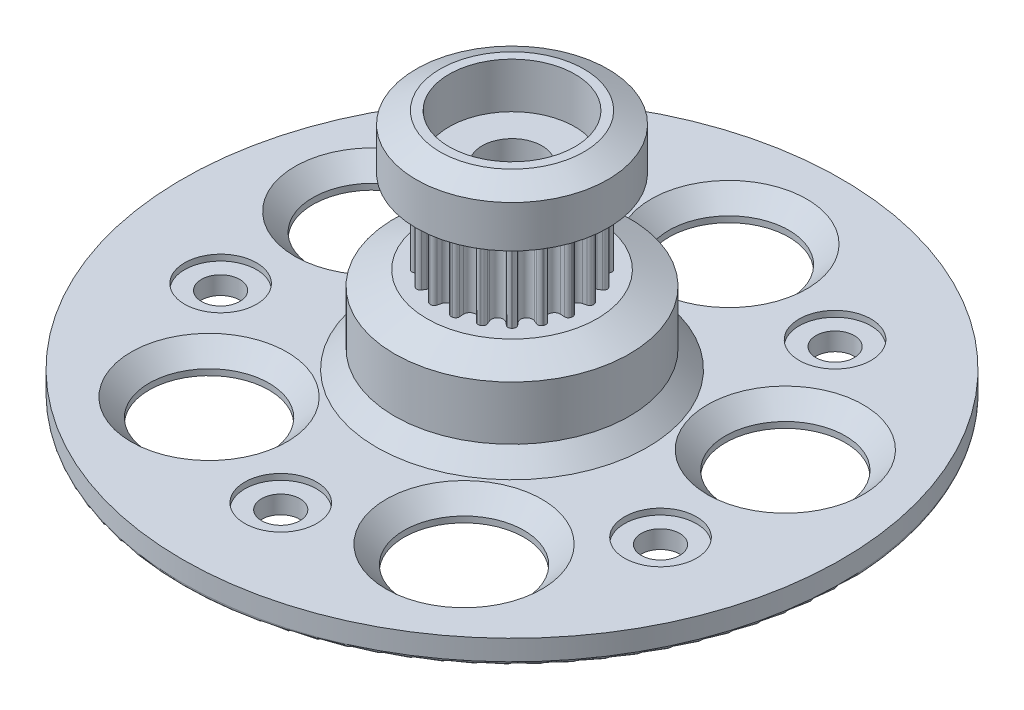
SolidWorks part; units mm, degrees
ref_plane "Frente" through (0, 0, 0) normal (0, 0, 1) x (1, 0, 0)
ref_plane "Topo" through (0, 0, 0) normal (0, 1, 0) x (1, 0, 0)
ref_plane "Lateral" through (0, 0, 0) normal (1, 0, 0) x (0, 0, -1)
sketch "Sketch1" plane through (0, 0, 0) normal (0, 1, 0) x (1, 0, 0)
  circle A0 centre (0, 0) radius 27.5
  dimension "D1" = 55
extrude "Boss-Extrude1" add sketch "Sketch1" along normal blind 2
sketch "Sketch2" plane through (0, 2, 0) normal (0, 1, 0) x (1, 0, 0)
  circle A0 centre (0, 0) radius 9.8
  dimension "D1" = 19.6
extrude "Boss-Extrude2" add sketch "Sketch2" along normal blind 6
chamfer "Chamfer1" distance 1.5 angle 45 1 edges at (0, 2, 9.8)
sketch "Sketch3" plane through (0, 8, 0) normal (0, 1, 0) x (1, 0, 0)
  circle A1 centre (0, 0) radius 9.8
  circle A2 centre (0, 0) radius 9.8
  dimension "D1" = 0
extrude "Boss-Extrude3" add sketch "Sketch3" along normal blind 1.2 draft 66
sketch "Sketch5" plane through (0, 9.2, 0) normal (0, 1, 0) x (1, 0, 0)
  circle A0 centre (0, 0) radius 6
  dimension "D1" = 12
extrude "Boss-Extrude4" add sketch "Sketch5" along normal blind 6
sketch "Sketch7" plane through (0, 15.2, 0) normal (0, 1, 0) x (1, 0, 0)
  line L0 (0, 5.5) -> (0, 0) construction
  line L1 (-0.4851, 5.379) -> (-0.6317, 5.9667)
  line L2 (0.4851, 5.379) -> (0.6317, 5.9667)
  arc A0 (-0.4851, 5.379) -> (0.4851, 5.379) centre (0, 5.5) ccw
  circle A1 centre (0, 0) radius 6 construction
  circle A2 centre (0, 0) radius 6 construction
  arc A3 (0.6317, 5.9667) -> (-0.6317, 5.9667) centre (0, 0) ccw
  dimension "D1" = 1
  dimension "D2" = 14
  dimension "D3" = 14
extrude "Cut-Extrude1" cut sketch "Sketch7" against normal up to surface (6 mm away) up to face at (0, 9.2, 6)
ref_axis "Axis1" through (0, 8, 0) along (0, -1, 0)
pattern_circular "CirPattern1" count 20 over 360 about axis through (0, 8, 0) along (0, -1, 0) of "Cut-Extrude1"
fillet "Fillet1" radius 0.3 40 edges at (0.6317, 12.2, -5.9667) (-0.6317, 12.2, -5.9667) (1.2431, 12.2, -5.8698) (-1.2431, 12.2, -5.8698) (2.4445, 12.2, -5.4794) (2.9961, 12.2, -5.1984) (4.0181, 12.2, -4.4558) (5.1984, 12.2, -2.9961) (4.4558, 12.2, -4.0181) (5.4794, 12.2, -2.4445) (5.8698, 12.2, -1.2431) (5.9667, 12.2, -0.6317) (5.9667, 12.2, 0.6317) (5.8698, 12.2, 1.2431) (5.4794, 12.2, 2.4445) (5.1984, 12.2, 2.9961) (4.4558, 12.2, 4.0181) (4.0181, 12.2, 4.4558) (2.9961, 12.2, 5.1984) (2.4445, 12.2, 5.4794) (1.2431, 12.2, 5.8698) (0.6317, 12.2, 5.9667) (-0.6317, 12.2, 5.9667) (-1.2431, 12.2, 5.8698) (-2.9961, 12.2, 5.1984) (-4.0181, 12.2, 4.4558) (-4.4558, 12.2, 4.0181) (-5.1984, 12.2, 2.9961) (-5.4794, 12.2, 2.4445) (-5.8698, 12.2, 1.2431) (-5.9667, 12.2, 0.6317) (-5.9667, 12.2, -0.6317) (-5.8698, 12.2, -1.2431) (-5.4794, 12.2, -2.4445) (-5.1984, 12.2, -2.9961) (-4.4558, 12.2, -4.0181) (-4.0181, 12.2, -4.4558) (-2.9961, 12.2, -5.1984) (-2.4445, 12.2, -5.4794) (-2.4445, 12.2, 5.4794)
sketch "Sketch9" plane through (0, 0, 0) normal (1, 0, 0) x (0, 0, -1)
  line L0 (0, 15.2) -> (6, 15.2)
  line L1 (0.4851, 15.2) -> (-0.4851, 15.2) construction
  line L2 (6, 15.2) -> (8, 16.2)
  line L3 (8, 16.2) -> (8, 19.7)
  line L4 (8, 19.7) -> (6, 20.7)
  line L5 (6, 20.7) -> (5.25, 20.7)
  line L6 (5.25, 20.7) -> (5.25, 16.9)
  line L7 (5.25, 16.9) -> (0, 16.9)
  line L8 (0, 16.9) -> (0, 15.2)
  dimension "D1" = 6
  dimension "D2" = 8
  dimension "D3" = 1
  dimension "D4" = 1
  dimension "D5" = 5.5
  dimension "D6" = 5.25
  dimension "D7" = 2
  dimension "D8" = 3.8
revolve "Revolve1" add sketch "Sketch9" angle 360 about L8
sketch "Sketch10" plane through (0, 2, 0) normal (0, 1, 0) x (1, 0, 0)
  line L0 (0, 11.3) -> (0, 13.1) construction
  line L1 (0, 13.1) -> (0, 27.5) construction
  circle A4 centre (0, 18.1) radius 5
  circle A7 centre (0, 0) radius 11.3 construction
  circle A8 centre (0, 0) radius 27.5 construction
  dimension "D1" = 10
  dimension "D2" = 1.8
extrude "Cut-Extrude2" cut sketch "Sketch10" against normal through all
chamfer "Chamfer2" distance 1.5 angle 45 1 edges at (0, 2, -13.1)
sketch "Sketch11" plane through (0, 2, 0) normal (0, 1, 0) x (1, 0, 0)
  line L0 (0, 0) -> (-11.3443, 15.614) construction
  line L1 (0, 0) -> (0, 19.3) construction
  circle A0 centre (0, 0) radius 19.3 construction
  circle A1 centre (0, 0) radius 11.3 construction
  circle A2 centre (-11.3443, 15.614) radius 1.6
  dimension "D1" = 8
  dimension "D3" = 3.2
  dimension "D2" = 36
extrude "Cut-Extrude3" cut sketch "Sketch11" against normal through all
sketch "Sketch12" plane through (0, 2, 0) normal (0, 1, 0) x (1, 0, 0)
  circle A0 centre (-11.3443, 15.614) radius 3
  dimension "D1" = 6
extrude "Cut-Extrude4" cut sketch "Sketch12" against normal blind 0.5
pattern_circular "CirPattern2" count 5 over 360 about axis through (0, 8, 0) along (0, -1, 0) of "Cut-Extrude2", "Chamfer2", "Cut-Extrude3", "Cut-Extrude4"
sketch "Sketch13" plane through (0, 0, 0) normal (0, -1, 0) x (1, 0, 0)
  circle A0 centre (0, 0) radius 8.2
  dimension "D1" = 16.4
extrude "Cut-Extrude5" cut sketch "Sketch13" against normal blind 6.8
sketch "Sketch15" plane through (0, 0, 0) normal (0, -1, 0) x (1, 0, 0)
  line L1 (2.15, -10.9131) -> (-2.15, -10.9131)
  line L2 (2.15, -10.9131) -> (2.15, 0)
  line L3 (2.15, 0) -> (-2.15, 0)
  line L4 (-2.15, -10.9131) -> (-2.15, 0)
  circle A0 centre (0, 0) radius 8.2 construction
  arc A1 (-2.15, -7.9131) -> (2.15, -7.9131) centre (0, 0) ccw construction
  dimension "D1" = 4.3
  dimension "D2" = 3
extrude "Cut-Extrude6" cut sketch "Sketch15" against normal blind 1.8
pattern_circular "CirPattern3" count 5 over 360 about axis through (0, 8, 0) along (0, -1, 0) of "Cut-Extrude6"
sketch "Sketch16" plane through (0, 16.9, 0) normal (0, 1, 0) x (1, 0, 0)
  circle A0 centre (0, 0) radius 2.5
  dimension "D1" = 5
extrude "Cut-Extrude7" cut sketch "Sketch16" against normal offset from surface (9.9 mm away) 0.2 up to face at (0, 6.8, -8.2)
fillet "Fillet2" radius 0.3 1 edges at (0, 0, 27.5)
